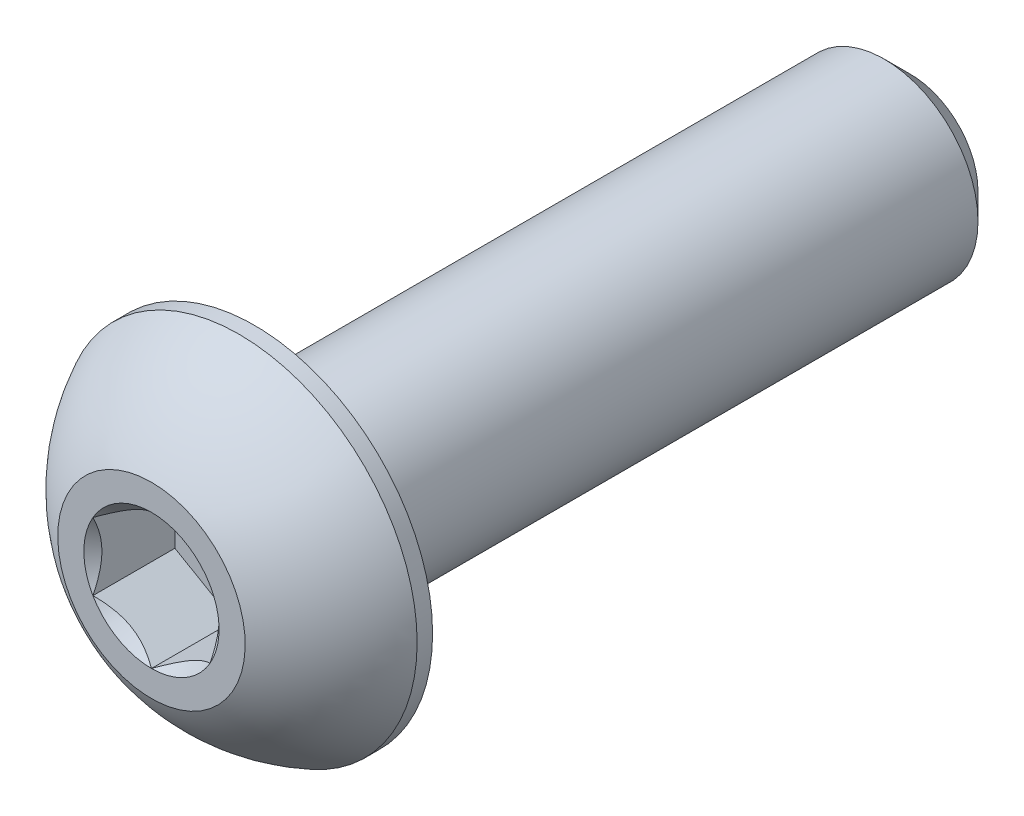
SolidWorks part; units mm, degrees
material "Alloy Steel"
ref_plane "Front Plane" through (0, 0, 0) normal (0, 0, 1) x (1, 0, 0)
ref_plane "Top Plane" through (0, 0, 0) normal (0, 1, 0) x (1, 0, 0)
ref_plane "Right Plane" through (0, 0, 0) normal (1, 0, 0) x (0, 0, -1)
sketch "Sketch1" plane through (0, 0, 0) normal (1, 0, 0) x (0, 0, -1)
  line L0 (-8.1, 0) -> (8.1, 0) construction
  line L1 (-5.9, 3.8) -> (-5.9, -3.8) construction
  line L2 (8.1, 2) -> (8.1, -2) construction
  line L3 (8.0562, 2.0758) -> (8.4062, 1.4696) construction
  line L4 (8.4062, 1.4696) -> (8.7562, 2.0758) construction
  line L5 (8.7562, 2.0758) -> (8.0562, 2.0758) construction
  line L6 (8.1, 2) -> (8.7125, 2) construction
  line L7 (8.4062, 2.0758) -> (8.4062, 2) construction
  line L8 (8.4062, 2) -> (8.4062, 1.5453) construction
  line L9 (8.4062, 1.5453) -> (8.4062, 1.4696) construction
  line L10 (8.3625, 1.5453) -> (8.45, 1.5453)
  line L11 (8.0781, 2.0379) -> (8.7344, 2.0379)
  line L12 (8.45, 1.5453) -> (8.7344, 2.0379)
  line L13 (8.3625, 1.5453) -> (8.0781, 2.0379)
  line L14 (-8.1, 1.25) -> (-8.1, -1.25) construction
  line L15 (8.1, 2) -> (-5.9, 2) construction
  point P3 (-5.9, 0)
  point P6 (-6.35, 0)
  point P21 (8.4062, 2.0379)
  point P24 (-6.23, 3.8)
  point P25 (6.35, -2)
  point P26 (-8.1, 2)
  dimension "Head Height" = 2.2
  dimension "Length" = 14
  dimension "Head Dia" = 7.6
  dimension "Thread Dia" = 4
  dimension "Pitch" = 0.7
  dimension "D2" = 0.0875
  dimension "Drive Size" = 2.5
  dimension "D1" = 1.75
  dimension "D3" = 0.33
  dimension "D4" = 1.75
sketch "Sketch2" plane through (0, 0, 0) normal (1, 0, 0) x (0, 0, -1)
  line L0 (-8.1, 0) -> (8.1, 0)
  line L1 (8.1, 0) -> (8.1, 1.44)
  line L2 (8.1, 2) -> (8.1, -2) construction
  line L3 (8.1, 1.44) -> (7.54, 2)
  line L4 (7.54, 2) -> (-5.9, 2)
  line L5 (-5.9, 3.8) -> (-5.9, -3.8) construction
  line L6 (-5.9, 2) -> (-5.9, 3.8)
  line L7 (-5.9, 3.8) -> (-6.23, 3.8)
  line L8 (8.1, 2) -> (8.7125, 2) construction
  line L9 (-8.1, 0) -> (-8.1, 2)
  arc A0 (-8.1, 2) -> (-6.23, 3.8) centre (-4.3736, 0) cw
  dimension "D1" = 0.56
  dimension "D2" = 45
revolve "Revolve1" add sketch "Sketch2" angle 360 about L0
sketch "Sketch3" plane through (0, 0, 8.1) normal (0, 0, 1) x (1, 0, 0)
  line L1 (0, 1.4434) -> (-1.25, 0.7217)
  line L2 (-1.25, 0.7217) -> (-1.25, -0.7217)
  line L3 (-1.25, -0.7217) -> (0, -1.4434)
  line L4 (0, -1.4434) -> (1.25, -0.7217)
  line L5 (1.25, -0.7217) -> (1.25, 0.7217)
  line L6 (1.25, 0.7217) -> (0, 1.4434)
  circle A0 centre (0, 0) radius 1.25 construction
  dimension "D1" = 2.5
extrude "Cut-Extrude1" cut sketch "Sketch3" against normal up to vertex (1.75 mm away) up to point (0, 0, 6.35)
sketch "Sketch4" plane through (0, 0, 8.1) normal (0, 0, 1) x (1, 0, 0)
  circle A0 centre (0, 0) radius 1.4434
extrude "Cut-Extrude2" cut sketch "Sketch4" against normal blind 10 draft 45
split "Split1" [suppressed] bodies to split 106
sketch "Sketch5" [suppressed] plane through (0, 0, -8.1) normal (0, 0, -1) x (-1, 0, 0)
  circle A0 centre (0, 0) radius 2 construction
  circle A1 centre (0, 0) radius 2
curve "Helix/Spiral1" [suppressed] pitch 0.7 height 14.7 turns 21
sketch "Sketch6" [suppressed] plane through (0, 0, 0) normal (1, 0, 0) x (0, 0, -1)
  line L0 (8.3625, 1.5453) -> (8.45, 1.5453) construction
  line L1 (8.3625, 1.5453) -> (8.0781, 2.0379) construction
  line L2 (8.0781, 2.0379) -> (8.7344, 2.0379) construction
  line L3 (8.45, 1.5453) -> (8.7344, 2.0379) construction
  line L4 (8.3625, 1.5453) -> (8.45, 1.5453)
  line L5 (8.3625, 1.5453) -> (8.0781, 2.0379)
  line L6 (8.0781, 2.0379) -> (8.7344, 2.0379)
  line L7 (8.45, 1.5453) -> (8.7344, 2.0379)
sweep "Cut-Sweep1" [suppressed] cut profiles "Sketch6" path "Helix/Spiral1"
sketch "Sketch7" [suppressed] plane through (0, 0, 5.9) normal (0, 0, -1) x (-1, 0, 0)
  circle A1 centre (0, 0) radius 2
  circle A2 centre (0, 0) radius 2
  dimension "D1" = 0
extrude "Boss-Extrude1" [suppressed] add sketch "Sketch7" along normal blind 10 draft 30
equation "\"D2@Sketch1\" = \"Pitch@Sketch1\" / 8"
equation "\"D1@Sketch1\"=\"Drive Size@Sketch1\"*.7"
equation "\"D3@Sketch1\"=\"Head Height@Sketch1\"*.15"
equation "\"D1@Sketch2\"=\"Pitch@Sketch1\"*.8"
equation "\"D1@Sketch3\"=\"Drive Size@Sketch1\""
equation "\"D4@Helix/Spiral1\"=\"Pitch@Sketch1\""
equation "\"D3@Helix/Spiral1\"=\"Length@Sketch1\"+\"Pitch@Sketch1\""
equation "\"D4@Sketch1\"=\"Pitch@Sketch1\"*2.5"
